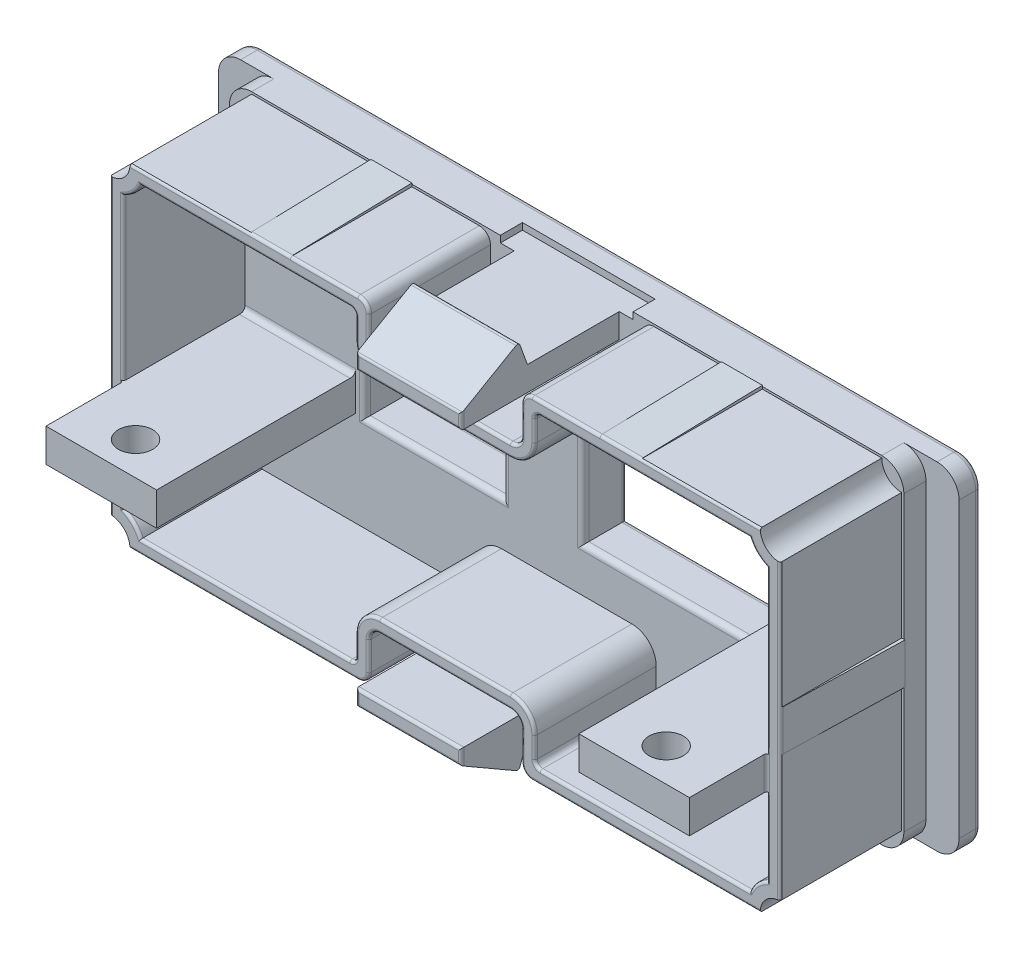
SolidWorks part; units mm, degrees
ref_plane "Front Plane" through (0, 0, 0) normal (0, 0, 1) x (1, 0, 0)
ref_plane "Top Plane" through (0, 0, 0) normal (0, 1, 0) x (1, 0, 0)
ref_plane "Right Plane" through (0, 0, 0) normal (1, 0, 0) x (0, 0, -1)
sketch "Sketch1" plane through (0, 0, 0) normal (0, 0, 1) x (1, 0, 0)
  line L1 (-31.5, 15.25) -> (31.5, 15.25)
  line L2 (-33.5, 13.25) -> (-33.5, -13.25)
  line L3 (-31.5, -15.25) -> (31.5, -15.25)
  line L4 (33.5, 13.25) -> (33.5, -13.25)
  line L5 (-33.5, 15.25) -> (33.5, -15.25) construction
  line L6 (-33.5, -15.25) -> (33.5, 15.25) construction
  arc A0 (-33.5, -13.25) -> (-31.5, -15.25) centre (-31.5, -13.25) ccw
  arc A1 (31.5, -15.25) -> (33.5, -13.25) centre (31.5, -13.25) ccw
  arc A2 (31.5, 15.25) -> (33.5, 13.25) centre (31.5, 13.25) cw
  arc A3 (-31.5, 15.25) -> (-33.5, 13.25) centre (-31.5, 13.25) ccw
  dimension "D1" = 2
  dimension "D2" = 30.5
  dimension "D3" = 67
extrude "Boss-Extrude1" add sketch "Sketch1" along normal blind 2
fillet "Fillet2" radius 0.5 8 edges at (0, -15.25, 0) (32.9142, -14.6642, 0) (33.5, 0, 0) (32.9142, 14.6642, 0) (0, 15.25, 0) (-32.9142, 14.6642, 0) (-33.5, 0, 0) (-32.9142, -14.6642, 0)
sketch "Sketch2" plane through (0, 0, 2) normal (0, 0, 1) x (1, 0, 0)
  line L1 (-28.5, 15.25) -> (28.5, 15.25)
  line L2 (-30.5, 13.25) -> (-30.5, -13.25)
  line L3 (-28.5, -15.25) -> (28.5, -15.25)
  line L4 (30.5, 13.25) -> (30.5, -13.25)
  line L5 (-30.5, 15.25) -> (30.5, -15.25) construction
  line L6 (-30.5, -15.25) -> (30.5, 15.25) construction
  line L7 (31.5, 15.25) -> (-31.5, 15.25) construction
  line L8 (33.5, -13.25) -> (33.5, 13.25) construction
  arc A0 (-30.5, -13.25) -> (-28.5, -15.25) centre (-28.5, -13.25) ccw
  arc A1 (28.5, -15.25) -> (30.5, -13.25) centre (28.5, -13.25) ccw
  arc A2 (28.5, 15.25) -> (30.5, 13.25) centre (28.5, 13.25) cw
  arc A3 (-28.5, 15.25) -> (-30.5, 13.25) centre (-28.5, 13.25) ccw
  point P0 (0, 0)
  dimension "D2" = 2
  dimension "D1" = 3
extrude "Boss-Extrude2" add sketch "Sketch2" along normal blind 2
sketch "Sketch4" plane through (0, 0, 0) normal (0, 0, -1) x (-1, 0, 0)
  line L0 (31.5, -15.25) -> (-31.5, -15.25) construction
  line L1 (-18.5, 8.75) -> (-1.5, 8.75)
  line L2 (-18.5, 8.75) -> (-18.5, -5.25)
  line L3 (-18.5, -5.25) -> (-1.5, -5.25)
  line L4 (-1.5, 8.75) -> (-1.5, -5.25)
  line L5 (-18.5, 8.75) -> (-1.5, -5.25) construction
  line L6 (-18.5, -5.25) -> (-1.5, 8.75) construction
  line L7 (5.75, 5.75) -> (18.25, 5.75)
  line L8 (5.75, 5.75) -> (5.75, -5.25)
  line L9 (5.75, -5.25) -> (18.25, -5.25)
  line L10 (18.25, 5.75) -> (18.25, -5.25)
  line L11 (5.75, 5.75) -> (18.25, -5.25) construction
  line L12 (5.75, -5.25) -> (18.25, 5.75) construction
  point P0 (-10, 1.75)
  point P5 (12, 0.25)
  dimension "D1" = 10
  dimension "D2" = 14
  dimension "D3" = 17
  dimension "D4" = 12.5
  dimension "D5" = 11
  dimension "D6" = 10
  dimension "D7" = 12
extrude "Cut-Extrude1" cut sketch "Sketch4" against normal through all
fillet "Fillet3" radius 0.5 8 edges at (-12, -5.25, 0) (-18.25, 0.25, 0) (-12, 5.75, 0) (-5.75, 0.25, 0) (1.5, 1.75, 0) (10, 8.75, 0) (18.5, 1.75, 0) (10, -5.25, 0)
sketch "Sketch5" plane through (0, 0, 4) normal (0, 0, 1) x (1, 0, 0)
  line L1 (28.5, 15.25) -> (-28.5, 15.25) construction
  line L3 (-28.5, -15.25) -> (28.5, -15.25) construction
  line L8 (-6.9, 14.05) -> (-6.9, 11.45)
  line L9 (-5.9, 10.45) -> (5.9, 10.45)
  line L10 (6.9, 11.45) -> (6.9, 14.05)
  line L11 (-28.5, 15.05) -> (-7.9, 15.05)
  line L12 (7.9, 15.05) -> (28.5, 15.05)
  line L13 (27.5505, -13.85) -> (8.1, -13.85)
  line L14 (-6.9, -14.05) -> (-6.9, -11.45)
  line L15 (-5.9, -10.45) -> (5.9, -10.45)
  line L16 (-30.3, 13.25) -> (-30.3, -13.25)
  line L17 (-30.5, 13.25) -> (-30.5, -13.25) construction
  line L18 (6.9, -11.45) -> (6.9, -14.05)
  line L19 (-30.5, 13.25) -> (-30.5, -13.25) construction
  line L20 (-7.9, -15.05) -> (-28.5, -15.05)
  line L21 (30.3, 13.25) -> (30.3, -13.25)
  line L22 (8.1, -11.45) -> (8.1, -13.85)
  line L23 (-5.9, -9.25) -> (5.9, -9.25)
  line L24 (-8.1, -13.85) -> (-8.1, -11.45)
  line L25 (-8.1, -13.85) -> (-27.5505, -13.85)
  line L26 (-29.1, 12.3005) -> (-29.1, -12.3005)
  line L27 (-27.5505, 13.85) -> (-8.1, 13.85)
  line L28 (28.5, -15.05) -> (7.9, -15.05)
  line L29 (-8.1, 13.85) -> (-8.1, 11.45)
  line L30 (-5.9, 9.25) -> (5.9, 9.25)
  line L31 (8.1, 11.45) -> (8.1, 13.85)
  line L32 (8.1, 13.85) -> (27.5505, 13.85)
  line L33 (29.1, 12.3005) -> (29.1, -12.3005)
  arc A1 (30.3, -13.25) -> (28.5, -15.05) centre (30.3, -15.05) ccw
  arc A2 (28.5, 15.05) -> (30.3, 13.25) centre (30.3, 15.05) ccw
  arc A3 (-28.5, 15.05) -> (-30.3, 13.25) centre (-30.3, 15.05) cw
  arc A4 (-28.5, -15.05) -> (-30.3, -13.25) centre (-30.3, -15.05) ccw
  arc A5 (6.9, -14.05) -> (7.9, -15.05) centre (7.9, -14.05) ccw
  arc A6 (5.9, -10.45) -> (6.9, -11.45) centre (5.9, -11.45) cw
  arc A7 (-6.9, -14.05) -> (-7.9, -15.05) centre (-7.9, -14.05) cw
  arc A8 (-6.9, -11.45) -> (-5.9, -10.45) centre (-5.9, -11.45) cw
  arc A9 (6.9, 14.05) -> (7.9, 15.05) centre (7.9, 14.05) cw
  arc A10 (5.9, 10.45) -> (6.9, 11.45) centre (5.9, 11.45) ccw
  arc A11 (-6.9, 11.45) -> (-5.9, 10.45) centre (-5.9, 11.45) ccw
  arc A12 (-6.9, 14.05) -> (-7.9, 15.05) centre (-7.9, 14.05) ccw
  arc A13 (8.1, -13.85) -> (8.1, -13.85) centre (8.1, -13.85) ccw
  arc A14 (5.9, -9.25) -> (8.1, -11.45) centre (5.9, -11.45) cw
  arc A15 (-8.1, -11.45) -> (-5.9, -9.25) centre (-5.9, -11.45) cw
  arc A16 (-8.1, -13.85) -> (-8.1, -13.85) centre (-8.1, -13.85) cw
  arc A17 (-27.5505, -13.85) -> (-29.1, -12.3005) centre (-30.3, -15.05) ccw
  arc A18 (-27.5505, 13.85) -> (-29.1, 12.3005) centre (-30.3, 15.05) cw
  arc A19 (-8.1, 13.85) -> (-8.1, 13.85) centre (-8.1, 13.85) ccw
  arc A20 (-8.1, 11.45) -> (-5.9, 9.25) centre (-5.9, 11.45) ccw
  arc A21 (5.9, 9.25) -> (8.1, 11.45) centre (5.9, 11.45) ccw
  arc A22 (8.1, 13.85) -> (8.1, 13.85) centre (8.1, 13.85) cw
  arc A23 (27.5505, 13.85) -> (29.1, 12.3005) centre (30.3, 15.05) ccw
  arc A24 (29.1, -12.3005) -> (27.5505, -13.85) centre (30.3, -15.05) ccw
  point P6 (0, 10.45)
  dimension "D4" = 1
  dimension "D1" = 0.2
  dimension "D2" = 0.2
  dimension "D3" = 4.6
  dimension "D6" = 13.8
  dimension "D5" = 0.2
  dimension "D7" = 0.2
  dimension "D8" = 1.2
extrude "Boss-Extrude3" add sketch "Sketch5" along normal blind 11
fillet "Fillet5" radius 0.5 4 edges at (-8.1, -13.85, 9.5) (8.1, -13.85, 9.5) (8.1, 13.85, 9.5) (-8.1, 13.85, 9.5)
sketch "Sketch6" plane through (0, 0, 4) normal (0, 0, 1) x (1, 0, 0)
  line L1 (-6, 15.25) -> (6, 15.25)
  line L2 (-6, 15.25) -> (-6, 14.65)
  line L3 (-6, 14.65) -> (6, 14.65)
  line L4 (6, 15.25) -> (6, 14.65)
  line L5 (-6, 15.25) -> (6, 14.65) construction
  line L6 (-6, 14.65) -> (6, 15.25) construction
  line L7 (-6, -14.65) -> (6, -14.65)
  line L8 (-6, -14.65) -> (-6, -15.25)
  line L9 (-6, -15.25) -> (6, -15.25)
  line L10 (6, -14.65) -> (6, -15.25)
  line L11 (-6, -14.65) -> (6, -15.25) construction
  line L12 (-6, -15.25) -> (6, -14.65) construction
  line L13 (28.5, 15.25) -> (-28.5, 15.25) construction
  line L14 (-28.5, -15.25) -> (28.5, -15.25) construction
  point P0 (0, 14.95)
  point P5 (0, -14.95)
  dimension "D1" = 12
  dimension "D2" = 0.6
extrude "Cut-Extrude2" cut sketch "Sketch6" against normal blind 2
sketch "Sketch7" plane through (0, 0, 4) normal (0, 0, 1) x (1, 0, 0)
  line L0 (-6, 14.65) -> (6, 14.65) construction
  line L1 (-4.75, 14.65) -> (4.75, 14.65)
  line L2 (-4.75, 14.65) -> (-4.75, 12.45)
  line L3 (-4.75, 12.45) -> (4.75, 12.45)
  line L4 (4.75, 14.65) -> (4.75, 12.45)
  line L5 (-4.75, 14.65) -> (4.75, 12.45) construction
  line L6 (-4.75, 12.45) -> (4.75, 14.65) construction
  line L7 (-4.75, -12.45) -> (4.75, -12.45)
  line L8 (-4.75, -12.45) -> (-4.75, -14.65)
  line L9 (-4.75, -14.65) -> (4.75, -14.65)
  line L10 (4.75, -12.45) -> (4.75, -14.65)
  line L11 (-4.75, -12.45) -> (4.75, -14.65) construction
  line L12 (-4.75, -14.65) -> (4.75, -12.45) construction
  line L13 (6, -14.65) -> (-6, -14.65) construction
  point P0 (0, 13.55)
  point P5 (0, -13.55)
  dimension "D1" = 2.2
  dimension "D2" = 9.5
extrude "Boss-Extrude4" add sketch "Sketch7" along normal blind 8.3
sketch "Sketch10" plane through (0, 0, 12.3) normal (0, 0, 1) x (1, 0, 0)
  line L0 (6, 15.25) -> (-6, 15.25) construction
  line L1 (-4.75, 17.25) -> (4.75, 17.25)
  line L2 (-4.75, 17.25) -> (-4.75, 12.45)
  line L3 (-4.75, 12.45) -> (4.75, 12.45)
  line L4 (4.75, 17.25) -> (4.75, 12.45)
  line L5 (-4.75, 17.25) -> (4.75, 12.45) construction
  line L6 (-4.75, 12.45) -> (4.75, 17.25) construction
  line L8 (-4.75, 12.45) -> (4.75, 12.45) construction
  line L9 (4.75, 12.45) -> (4.75, 14.65) construction
  line L10 (-4.75, 14.65) -> (-4.75, 12.45) construction
  point P0 (0, 14.85)
  dimension "D1" = 2
extrude "Boss-Extrude5" add sketch "Sketch10" along normal blind 6
sketch "Sketch11" plane through (0, 0, 12.3) normal (0, 0, 1) x (1, 0, 0)
  line L0 (4.75, -14.65) -> (4.75, -12.45) construction
  line L1 (-4.75, -12.45) -> (4.75, -12.45)
  line L2 (-4.75, -12.45) -> (-4.75, -17.25)
  line L3 (-4.75, -17.25) -> (4.75, -17.25)
  line L4 (4.75, -12.45) -> (4.75, -17.25)
  line L5 (-4.75, -12.45) -> (4.75, -17.25) construction
  line L6 (-4.75, -17.25) -> (4.75, -12.45) construction
  line L7 (-4.75, -12.45) -> (-4.75, -14.65) construction
  line L8 (4.75, -12.45) -> (-4.75, -12.45) construction
  line L9 (-6, -15.25) -> (6, -15.25) construction
  point P0 (0, -14.85)
  dimension "D1" = 2
extrude "Boss-Extrude6" add sketch "Sketch11" along normal blind 6
draft "Draft3" type of draft neutral plane draft angle 30 faces to draft 1 face at (0, 17.25, 15.3) neutral plane through (0, 0, 12.3) neutral plane normal (0, 0, -1) reverse direction yes parameters "D1"=30
draft "Draft4" type of draft neutral plane draft angle 20 faces to draft 1 face at (0, 15.95, 12.3) neutral plane through (-6, 14.65, 2) neutral plane normal (0, 1, 0) parameters "D1"=20
draft "Draft5" type of draft neutral plane draft angle 30 faces to draft 1 face at (0, -17.25, 15.3) neutral plane through (0, 0, 12.3) neutral plane normal (0, 0, -1) reverse direction yes parameters "D1"=30
draft "Draft6" type of draft neutral plane draft angle 20 faces to draft 1 face at (0, -15.95, 12.3) neutral plane through (-6, -14.65, 2) neutral plane normal (0, -1, 0) parameters "D1"=20
fillet "Fillet11" radius 0.25 10 edges at (0, -13.7859, 18.3) (-4.75, -13.1179, 18.3) (0, -12.45, 18.3) (4.75, -13.1179, 18.3) (0, 12.45, 18.3) (-4.75, 13.1179, 18.3) (0, 13.7859, 18.3) (4.75, 13.1179, 18.3) (0, -16.7985, 13.082) (0, 16.7985, 13.082)
sketch "Sketch12" plane through (0, 15.05, 0) normal (0, 1, 0) x (1, 0, 0)
  line L0 (-7.9, -4) -> (-28.5, -4) construction
  line L1 (14, -4) -> (17.7, -4)
  line L2 (14, -4) -> (14, -15)
  line L3 (14, -15) -> (17.7, -15)
  line L4 (17.7, -4) -> (17.7, -15)
  line L5 (14, -4) -> (17.7, -15) construction
  line L6 (14, -15) -> (17.7, -4) construction
  line L7 (-17.7, -4) -> (-14, -4)
  line L8 (-17.7, -4) -> (-17.7, -15)
  line L9 (-17.7, -15) -> (-14, -15)
  line L10 (-14, -4) -> (-14, -15)
  line L11 (-17.7, -4) -> (-14, -15) construction
  line L12 (-17.7, -15) -> (-14, -4) construction
  line L13 (-7.9, -15) -> (-28.5, -15) construction
  point P0 (15.85, -9.5)
  point P5 (-15.85, -9.5)
  dimension "D1" = 3.7
  dimension "D2" = 14
  dimension "D3" = 14
extrude "Boss-Extrude7" add sketch "Sketch12" along normal blind 0.3
sketch "Sketch14" plane through (0, -15.05, 0) normal (0, -1, 0) x (1, 0, 0)
  line L0 (14, 15) -> (17.7, 15)
  line L1 (14, 15) -> (14, 4)
  line L2 (14, 4) -> (17.7, 4)
  line L3 (17.7, 15) -> (17.7, 4)
  line L4 (14, 15) -> (17.7, 4) construction
  line L5 (14, 4) -> (17.7, 15) construction
  line L6 (-17.7, 15) -> (-14, 15)
  line L7 (-17.7, 15) -> (-17.7, 4)
  line L8 (-17.7, 4) -> (-14, 4)
  line L9 (-14, 15) -> (-14, 4)
  line L10 (-17.7, 15) -> (-14, 4) construction
  line L11 (-17.7, 4) -> (-14, 15) construction
  line L12 (-28.5, 4) -> (-7.9, 4) construction
  line L19 (7.9, 4) -> (28.5, 4) construction
  point P0 (15.85, 9.5)
  point P5 (-15.85, 9.5)
  dimension "D1" = 3.7
  dimension "D2" = 14
  dimension "D3" = 14
extrude "Boss-Extrude10" add sketch "Sketch14" along normal blind 0.3
sketch "Sketch15" plane through (-30.3, 0, 0) normal (-1, 0, 0) x (0, 0, 1)
  line L0 (4, 13.25) -> (4, -13.25) construction
  line L1 (4, 1.85) -> (15, 1.85)
  line L2 (4, 1.85) -> (4, -1.85)
  line L3 (4, -1.85) -> (15, -1.85)
  line L4 (15, 1.85) -> (15, -1.85)
  line L5 (4, 1.85) -> (15, -1.85) construction
  line L6 (4, -1.85) -> (15, 1.85) construction
  line L7 (15, 13.25) -> (15, -13.25) construction
  point P0 (9.5, 0)
  dimension "D1" = 3.7
extrude "Boss-Extrude11" add sketch "Sketch15" along normal blind 0.3
sketch "Sketch16" plane through (30.3, 0, 0) normal (1, 0, 0) x (0, 0, -1)
  line L0 (-4, -13.25) -> (-4, 13.25) construction
  line L1 (-15, 1.85) -> (-4, 1.85)
  line L2 (-15, 1.85) -> (-15, -1.85)
  line L3 (-15, -1.85) -> (-4, -1.85)
  line L4 (-4, 1.85) -> (-4, -1.85)
  line L5 (-15, 1.85) -> (-4, -1.85) construction
  line L6 (-15, -1.85) -> (-4, 1.85) construction
  line L7 (-15, -13.25) -> (-15, 13.25) construction
  point P0 (-9.5, 0)
  dimension "D1" = 3.7
extrude "Boss-Extrude12" add sketch "Sketch16" along normal blind 0.3
sketch "Sketch17" plane through (0, 0, 4) normal (0, 0, 1) x (1, 0, 0)
  line L0 (-29.1, 12.3005) -> (-29.1, -12.3005) construction
  line L1 (-29.1, -2.25) -> (-19.1, -2.25)
  line L2 (-29.1, -2.25) -> (-29.1, -5.25)
  line L3 (-29.1, -5.25) -> (-19.1, -5.25)
  line L4 (-19.1, -2.25) -> (-19.1, -5.25)
  line L5 (-29.1, -2.25) -> (-19.1, -5.25) construction
  line L6 (-29.1, -5.25) -> (-19.1, -2.25) construction
  line L7 (19.1, -2.25) -> (29.1, -2.25)
  line L8 (19.1, -2.25) -> (19.1, -5.25)
  line L9 (19.1, -5.25) -> (29.1, -5.25)
  line L10 (29.1, -2.25) -> (29.1, -5.25)
  line L11 (19.1, -2.25) -> (29.1, -5.25) construction
  line L12 (19.1, -5.25) -> (29.1, -2.25) construction
  line L13 (29.1, -12.3005) -> (29.1, 12.3005) construction
  line L17 (-5.75, -5.25) -> (-18.25, -5.25) construction
  point P0 (-24.1, -3.75)
  point P5 (24.1, -3.75)
  dimension "D1" = 3
  dimension "D2" = 10
extrude "Boss-Extrude13" add sketch "Sketch17" along normal blind 18
sketch "Sketch19" plane through (0, -2.25, 0) normal (0, 1, 0) x (1, 0, 0)
  line L0 (-17.7, -4) -> (-28.5, -4) construction
  circle A0 centre (-24, -19) radius 1.55
  circle A1 centre (24, -19) radius 1.55
  dimension "D1" = 3.1
  dimension "D2" = 24
  dimension "D3" = 24
  dimension "D4" = 15
extrude "Cut-Extrude4" cut sketch "Sketch19" against normal through all
draft "Draft12" type of draft neutral plane draft angle 1.5 faces to draft 6 face at (-15.85, -15.35, 9.5) face at (15.85, -15.35, 9.5) face at (30.6, 0, 9.5) face at (-30.6, 0, 9.5) face at (15.85, 15.35, 9.5) face at (-15.85, 15.35, 9.5) neutral plane through (-28.5, -13.25, 4) neutral plane normal (0, 0, 1) parameters "D1"=1.5
fillet "Fillet20" radius 0.25 1 edges at (29.1, -3.75, 15)
fillet "Fillet21" radius 0.25 1 edges at (-29.1, -3.75, 15)
fillet "Fillet22" radius 0.25 13 edges at (-8.2464, -13.7036, 15) (8.2464, -13.7036, 15) (29.1, -8.7752, 15) (-29.1, -8.7752, 15) (-28.1787, -12.9287, 15) (-18.0752, -13.85, 15) (-8.1, -12.4, 15) (-7.4556, -9.8944, 15) (0, -9.25, 15) (7.4556, -9.8944, 15) (8.1, -12.4, 15) (18.0752, -13.85, 15) (28.1787, -12.9287, 15)
fillet "Fillet23" radius 0.25 13 edges at (8.2464, 13.7036, 15) (-8.2464, 13.7036, 15) (29.1, 5.0252, 15) (28.1787, 12.9287, 15) (18.0752, 13.85, 15) (8.1, 12.4, 15) (7.4556, 9.8944, 15) (0, 9.25, 15) (-7.4556, 9.8944, 15) (-8.1, 12.4, 15) (-18.0752, 13.85, 15) (-28.1787, 12.9287, 15) (-29.1, 5.0252, 15)
fillet "Fillet25" radius 0.25 1 edges at (15.85, -15.062, 15)
fillet "Fillet26" radius 0.25 1 edges at (-30.312, 0, 15)
fillet "Fillet27" radius 0.25 1 edges at (30.312, 0, 15)
fillet "Fillet28" radius 0.25 1 edges at (15.85, 15.062, 15)
fillet "Fillet29" radius 0.25 1 edges at (-15.85, -15.062, 15)
fillet "Fillet30" radius 0.25 9 edges at (10.95, -15.05, 14.8442) (6.9945, -14.4743, 15) (6.9, -12.75, 15) (6.6071, -10.7429, 15) (0, -10.45, 15) (-6.6071, -10.7429, 15) (-6.9, -12.75, 15) (-6.9945, -14.4743, 15) (-10.95, -15.05, 14.8442)
fillet "Fillet31" radius 0.25 9 edges at (10.95, 15.05, 14.8442) (6.9945, 14.4743, 15) (6.9, 12.75, 15) (6.6071, 10.7429, 15) (0, 10.45, 15) (-6.6071, 10.7429, 15) (-6.9, 12.75, 15) (-7.1929, 14.7571, 15) (-10.95, 15.05, 15)
fillet "Fillet32" radius 0.25 1 edges at (-15.85, 15.062, 15)
fillet "Fillet36" radius 0.5 8 edges at (10, -5.25, 4) (18.5, 1.75, 4) (10, 8.75, 4) (1.5, 1.75, 4) (-18.25, 0.25, 4) (-12, -5.25, 4) (-5.75, 0.25, 4) (-12, 5.75, 4) conic rho 0.5
fillet "Fillet37" radius 0.5 2 edges at (24.1, -2.25, 4) (-24.1, -2.25, 4) conic rho 0.5
